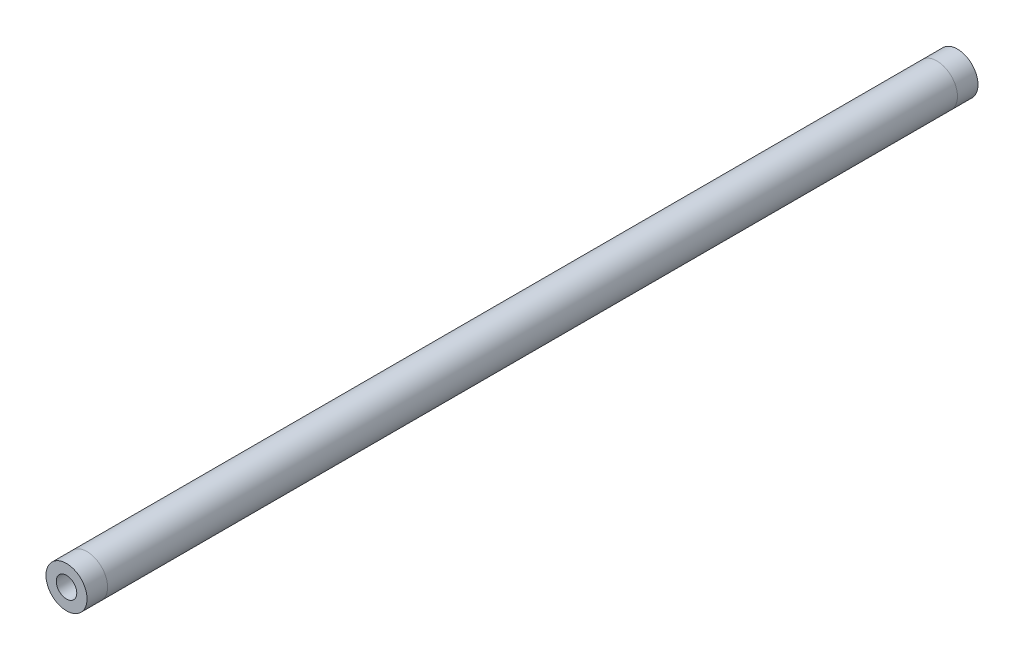
SolidWorks part; units mm, degrees
material "AISI 4130 Steel, annealed at 865C"
ref_plane "Front Plane" through (0, 0, 0) normal (0, 0, 1) x (1, 0, 0)
ref_plane "Top Plane" through (0, 0, 0) normal (0, 1, 0) x (1, 0, 0)
ref_plane "Right Plane" through (0, 0, 0) normal (1, 0, 0) x (0, 0, -1)
sketch "Axis" plane through (0, 0, 0) normal (1, 0, 0) x (0, 0, -1)
  line L0 (0, 0) -> (275.3894, 0) construction
  line L1 (275.3894, 0) -> (269.0394, 0)
  line L2 (275.3894, 0) -> (297.2842, 0) construction
  line L3 (0, 0) -> (-21.8948, 0) construction
  point P4 (0, 0)
  point P5 (275.3894, 0)
  point P6 (269.0394, 0)
  point P8 (297.2842, 0)
  dimension "D1" = 6.35
  dimension "D2" = 21.8948
  dimension "D3" = 21.8948
sketch "Sketch1" plane through (0, 0, 0) normal (0, 0, 1) x (1, 0, 0)
  circle A0 centre (0, 0) radius 6.35
  circle A1 centre (0, 0) radius 4.826
  circle A2 centre (0, 0) radius 3.175
  dimension "D1" = 12.7
  dimension "D2" = 1.524
  dimension "D3" = 6.35
extrude "Threaded insert 1-1" add sketch "Sketch1" against normal blind 6.35 contours A0 A1 | A1 A2 region at (-6.1704, 0, 0) region at (-4.6895, 0, 0)
extrude "Threaded insert 1-2" add sketch "Sketch1<3>" against normal blind 9.525 from surface contours A1 A2 region at (-4.6895, 0, 0) starting at face at (6.35, 0, -6.35)
sketch "Sketch1<3>" plane through (0, 0, 0) normal (0, 0, 1) x (1, 0, 0) same geometry as "Sketch1"
extrude "Tube extrude" add sketch "Sketch1<4>" against normal up to vertex (269.0394 mm away) from surface separate body contours A0 A1 region at (-6.1704, 0, 0) up to point (0, 0, -269.0394) starting at face at (4.826, 0, -6.35)
sketch "Sketch1<4>" plane through (0, 0, 0) normal (0, 0, 1) x (1, 0, 0) same geometry as "Sketch1"
extrude "Threaded insert 2-1" add sketch "Sketch1<6>" along normal blind 9.525 from surface separate body contours A1 A2 region at (-4.6895, 0, 0) starting at face at (4.826, 0, -269.0394)
sketch "Sketch1<6>" plane through (0, 0, 0) normal (0, 0, 1) x (1, 0, 0) same geometry as "Sketch1"
extrude "Threaded insert 2-2" add sketch "Sketch1<9>" against normal blind 6.35 from surface separate body contours A1 A2 | A0 A1 region at (-6.1704, 0, 0) region at (-4.6895, 0, 0) starting at face at (4.826, 0, -269.0394)
sketch "Sketch1<9>" plane through (0, 0, 0) normal (0, 0, 1) x (1, 0, 0) same geometry as "Sketch1"
combine bodies "Combine1" operation type add bodies to combine 106 104
equation "\"Threaded insert outer thickness\"= .25"
equation "\"D1@Threaded insert 1-1\"=\"Threaded insert outer thickness\""
equation "\"D1@Threaded insert 2-2\"=\"Threaded insert outer thickness\""
equation "\"D1@Axis\" = \"Threaded insert outer thickness\""
